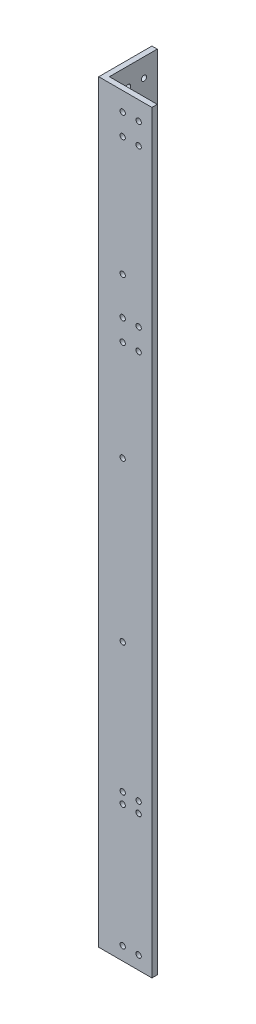
SolidWorks part; units mm, degrees
ref_plane "Front Plane" through (0, 0, 0) normal (0, 0, 1) x (1, 0, 0)
ref_plane "Top Plane" through (0, 0, 0) normal (0, 1, 0) x (1, 0, 0)
ref_plane "Right Plane" through (0, 0, 0) normal (1, 0, 0) x (0, 0, -1)
sketch "Sketch2" plane through (0, 0, 0) normal (0, 1, 0) x (1, 0, 0)
  line L0 (0, 31.75) -> (3.175, 31.75)
  line L1 (3.175, 31.75) -> (3.175, 3.175)
  line L2 (3.175, 3.175) -> (31.75, 3.175)
  line L3 (31.75, 3.175) -> (31.75, 0)
  line L4 (31.75, 0) -> (0, 0)
  line L5 (0, 0) -> (0, 31.75)
  point P9 (1.5875, 31.75)
  point P10 (31.75, 1.5875)
  dimension "D4" = 3.175
  dimension "D1" = 31.75
  dimension "D2" = 31.75
  dimension "D3" = 3.175
extrude "Boss-Extrude1" add sketch "Sketch2" along normal blind 450
sketch "RightSideHoles-Sketch3" plane through (0, 0, 0) normal (0, 0, 1) x (1, 0, 0)
  line L0 (0, 0) -> (31.75, 0) construction
  line L3 (0, 450) -> (0, 0) construction
  circle A0 centre (14.2875, 81.1125) radius 1.5875
  circle A1 centre (23.8125, 81.1125) radius 1.5875
  circle A2 centre (14.2875, 87.4625) radius 1.5875
  circle A3 centre (23.8125, 87.4625) radius 1.5875
  circle A4 centre (14.2875, 438.8875) radius 1.5875
  circle A5 centre (14.2875, 426.1875) radius 1.5875
  circle A6 centre (23.8125, 438.8875) radius 1.5875
  circle A7 centre (23.8125, 426.1875) radius 1.5875
  circle A8 centre (14.2875, 332.6026) radius 1.5875
  circle A9 centre (23.8125, 332.6026) radius 1.5875
  circle A10 centre (14.2875, 319.9026) radius 1.5875
  circle A11 centre (23.8125, 319.9026) radius 1.5875
  circle A12 centre (14.2875, 7.9375) radius 1.5875
  circle A13 centre (23.8125, 7.9375) radius 1.5875
  circle A14 centre (14.2875, 165) radius 1.5875
  circle A15 centre (14.2875, 260) radius 1.5875
  circle A16 centre (14.2875, 355) radius 1.5875
  dimension "D4" = 3.175
  dimension "D1" = 81.1125
  dimension "D2" = 14.2875
  dimension "D8" = 11.1125
  dimension "D12" = 7.9375
  dimension "D5" = 6.35
  dimension "D7" = 12.7
  dimension "D9" = 12.7
  dimension "D3" = 9.525
  dimension "D10" = 332.6026
  dimension "D11" = 165
  dimension "D13" = 95
  dimension "D14" = 95
sketch "FrontSideHoles-Sketch4" plane through (0, 0, 0) normal (-1, 0, 0) x (0, 0, 1)
  line L0 (-31.75, 450) -> (0, 450) construction
  line L1 (0, 450) -> (0, 0) construction
  line L3 (-31.75, 0) -> (0, 0) construction
  circle A0 centre (-23.8125, 81.1125) radius 1.5875
  circle A1 centre (-14.2875, 81.1125) radius 1.5875
  circle A2 centre (-23.8125, 87.4625) radius 1.5875
  circle A3 centre (-14.2875, 87.4625) radius 1.5875
  circle A4 centre (-23.8125, 438.8875) radius 1.5875
  circle A5 centre (-14.2875, 438.8875) radius 1.5875
  circle A6 centre (-23.8125, 426.1875) radius 1.5875
  circle A7 centre (-14.2875, 426.1875) radius 1.5875
  circle A8 centre (-14.2875, 338.1776) radius 1.5875
  circle A9 centre (-14.2875, 319.6526) radius 1.5875
  circle A10 centre (-14.2875, 165) radius 1.5875
  circle A11 centre (-14.2875, 260) radius 1.5875
  circle A12 centre (-14.2875, 355) radius 1.5875
  circle A13 centre (-23.8125, 7.9375) radius 1.5875
  circle A14 centre (-14.2875, 7.9375) radius 1.5875
  dimension "D4" = 3.175
  dimension "D2" = 14.2875
  dimension "D5" = 6.35
  dimension "D7" = 12.7
  dimension "D13" = 95
  dimension "D14" = 95
  dimension "D3" = 81.1125
  dimension "D6" = 11.1125
  dimension "D9" = 18.525
  dimension "D10" = 14.2875
  dimension "D11" = 9.525
  dimension "D8" = 319.6526
  dimension "D12" = 165
  dimension "D15" = 7.9375
extrude "RightSideHoles-Cut-Extrude1" cut sketch "RightSideHoles-Sketch3" against normal blind 3.175
extrude "FrontSideHoles-Cut-Extrude2" cut sketch "FrontSideHoles-Sketch4" against normal blind 3.175
equation "\"RailThickness\"= .125in'Spec"
equation "\"VSWidth\"= 1.25in'Spec"
equation "\"VSHeight\"= 1.25in'Spec"
equation "\"VSLength\"= 450mm"
equation "\"HoleOffsetFromEdge\"= \"RailThickness\" * 2.5"
equation "\"HoleOffsetFromSide\"= \"RailThickness\" * 3.5"
equation "\"LegHeight\"= 70mm'Space needed for PSU/Stepper/Electronics"
equation "\"VSBottomSideRailHoleY1FromBottomOfLowerRail\"= \"V1 BottomOfLowerRail\" + \"HoleOffsetFromSide\"'Equals 70.1125"
equation "\"VSSideRailHoleX1FromSide\"= \"HoleOffsetFromSide\" + \"RailThickness\""
equation "\"FasteningHoleDiameter\"= .125in"
equation "\"VSBottomSideRailHoleY2FromY1\"= \"LowerRailHeight\" - \"HoleOffsetFromSide\" - \"HoleOffsetFromEdge\"'Equals 6.35"
equation "\"VSTopSideRailHoleY1FromEdge\"= \"HoleOffsetFromEdge\" + \"RailThickness\""
equation "\"D4@RightSideHoles-Sketch3\" = \"FasteningHoleDiameter\""
equation "\"D1@RightSideHoles-Sketch3\" = \"VSBottomSideRailHoleY1FromBottomOfLowerRail\""
equation "\"D2@RightSideHoles-Sketch3\" = \"VSSideRailHoleX1FromSide\""
equation "\"D1@Boss-Extrude1\"=\"VSLength\""
equation "\"D4@FrontSideHoles-Sketch4\" = \"FasteningHoleDiameter\""
equation "\"D3@FrontSideHoles-Sketch4\" = \"VSBottomSideRailHoleY1FromBottomOfLowerRail\""
equation "\"D2@FrontSideHoles-Sketch4\" = \"VSSideRailHoleX1FromSide\""
equation "\"D8@RightSideHoles-Sketch3\" = \"VSTopSideRailHoleY1FromEdge\""
equation "\"D6@FrontSideHoles-Sketch4\" = \"VSTopSideRailHoleY1FromEdge\""
equation "\"VSMidSideRailHoleY1FromV8TopOfMidSideRail\"= \"V8 ToTopOfMidSideRail\" - \"HoleOffsetFromEdge\"'Equals 308.2875"
equation "\"LowerRailHeight\"= 1.00in"
equation "\"D2@Sketch2\"=\"VSWidth\""
equation "\"D1@Sketch2\"=\"VSHeight\""
equation "\"TopRailHeight\"= 1.25in"
equation "\"MidSideRailHeight\"= 1.25in"
equation "\"D12@RightSideHoles-Sketch3\"=\"HoleOffsetFromEdge\""
equation "\"D5@RightSideHoles-Sketch3\"=\"VSBottomSideRailHoleY2FromY1\""
equation "\"D5@FrontSideHoles-Sketch4\"=\"VSBottomSideRailHoleY2FromY1\""
equation "\"VSMidSideRailHoleY2FromY1\"= \"MidSideRailHeight\" - \"HoleOffsetFromSide\" - \"HoleOffsetFromEdge\"'Equals 12.7"
equation "\"D7@RightSideHoles-Sketch3\"=\"VSMidSideRailHoleY2FromY1\""
equation "\"VSTopSideRailHoleY2FromY1\"= \"TopRailHeight\" - \"VSTopSideRailHoleY1FromEdge\" - \"HoleOffsetFromEdge\"'Equals 12.7"
equation "\"D9@RightSideHoles-Sketch3\"=\"VSTopSideRailHoleY2FromY1\""
equation "\"D7@FrontSideHoles-Sketch4\"=\"VSTopSideRailHoleY2FromY1\""
equation "\"VSSideRailHoleX2FromX1\"= \"VSWidth\" - \"VSSideRailHoleX1FromSide\" - \"HoleOffsetFromEdge\""
equation "\"D3@RightSideHoles-Sketch3\"=\"VSSideRailHoleX2FromX1\""
equation "\"D11@FrontSideHoles-Sketch4\"=\"VSSideRailHoleX2FromX1\""
equation "\"1mmSpacer\"= 1mm"
equation "\"20TGT2PulleyWidth\"= 8.7mm'The STL of the Pulley in the diagram is a bit larger"
equation "\"BeltTensionerUpperLowerWallThickness\"= 7mm"
equation "\"BeltTensionerInnerHeight\"= \"20TGT2PulleyWidth\" * 2 + \"1mmSpacer\" * 3"
equation "\"BeltTensionerHeight\"= \"BeltTensionerInnerHeight\" + \"BeltTensionerUpperLowerWallThickness\" * 2"
equation "\"D9@FrontSideHoles-Sketch4\"=\"VSBeltTensionerHoleY2FromY1\""
equation "\"VSBeltTensionerHoleY1FromBottom\"= \"V9 FromBottomGantryPulleyToBottomOfBeltTensioner\" + \"HoleOffsetFromEdge\""
equation "\"VSBeltTensionerHoleY2FromY1\"= \"BeltTensionerHeight\" - \"HoleOffsetFromEdge\" * 2"
equation "\"V1 BottomOfLowerRail\"= \"LegHeight\""
equation "\"StepperShaftLength\"= 24mm'Pulley will be attached to the end"
equation "\"ZAxisLeadScrewLength\"= 200mm"
equation "\"LM8UUHeight\"= 24mm'Spec"
equation "\"V2 ToBedAtTopOfZAxis\"= \"V1 BottomOfLowerRail\" + \"StepperShaftLength\" + \"ZAxisLeadScrewLength\" - \"LM8UUHeight\" / 2"
equation "\"HotEndToTopOfXAxisGB\"= 63.315144mm'Measured from the100.Should be 63.315144"
equation "\"TopOfGBToBottomOfLinearRail\"= \"LinearGBWidth\" / 2 + \"LinearRailWidth\" / 2"
equation "\"LinearGBWidth\"= 27mm'Spec"
equation "\"V5 ToBottomOfXAxisLinearRail\"= \"V4 ToTopOfBuildPlate/HotEndTip\" + \"HotEndToTopOfXAxisGB\" - \"TopOfGBToBottomOfLinearRail\""
equation "\"LinearRailWidth\"= 12mm'Spec"
equation "\"V6 ToBottomOfGantryPulley\"= \"V5 ToBottomOfXAxisLinearRail\" - \"DistanceFromGABTopToLowerPulley\""
equation "\"GABUpperHeight\"= 6mm"
equation "\"GABMidWallHeight\"= 28mm'Must equal 28 or changes alignment"
equation "\"GABMidShortRiserHeight\"= \"GABMidWallHeight\" / 2 - \"20TGT2PulleyWidth\"'Equals 5.3"
equation "\"GABRiserBossOffset\"= 0.8mm'Aligns Pulleys"
equation "\"DistanceFromGABTopToLowerPulley\"= \"GABUpperHeight\" + \"GABMidWallHeight\" - \"GABMidShortRiserHeight\" + \"GABRiserBossOffset\" / 2"
equation "\"V7 ToTopOfMidBackRail\"= \"V6 ToBottomOfGantryPulley\" + \"StepperShaftLength\""
equation "\"D10@RightSideHoles-Sketch3\"=\"VSMidSideRailHoleY1FromV8TopOfMidSideRail\""
equation "\"BedToBuildPlateStandoffLength\"= 15mm"
equation "\"BuildPlateHeight\"= 8mm'Spec"
equation "\"V4 ToTopOfBuildPlate/HotEndTip\"= \"V2 ToBedAtTopOfZAxis\" + \"BedToBuildPlateStandoffLength\" + \"BuildPlateHeight\""
equation "\"D8@FrontSideHoles-Sketch4\"=\"VSBeltTensionerHoleY1FromBottom\""
equation "\"V8 ToTopOfMidSideRail\"= \"V7 ToTopOfMidBackRail\" - \"RailThickness\""
equation "\"V9 FromBottomGantryPulleyToBottomOfBeltTensioner\"= \"V6 ToBottomOfGantryPulley\" - \"BeltTensionerUpperLowerWallThickness\" - \"1mmSpacer\""
equation "\"BeltTensionerMountingHoleOffsetFromEdge\"= \"HoleOffsetFromEdge\""
equation "\"VSBeltTensionerXMountingHoleOffsetFromSide\"= \"BeltTensionerMountingHoleOffsetFromEdge\" + \"RailThickness\" * 2"
equation "\"D10@FrontSideHoles-Sketch4\"=\"VSBeltTensionerXMountingHoleOffsetFromSide\""
equation "\"VSEnclosureOffsets\"= ( \"VSLength\" - \"LegHeight\" ) / 4"
equation "\"D11@RightSideHoles-Sketch3\"=\"LegHeight\" + \"VSEnclosureOffsets\""
equation "\"D13@RightSideHoles-Sketch3\"=\"VSEnclosureOffsets\""
equation "\"D14@RightSideHoles-Sketch3\"=\"VSEnclosureOffsets\""
equation "\"D12@FrontSideHoles-Sketch4\"= \"LegHeight\" + \"VSEnclosureOffsets\""
equation "\"D13@FrontSideHoles-Sketch4\"=\"VSEnclosureOffsets\""
equation "\"D14@FrontSideHoles-Sketch4\"=\"VSEnclosureOffsets\""
equation "\"D15@FrontSideHoles-Sketch4\"=\"HoleOffsetFromEdge\""
